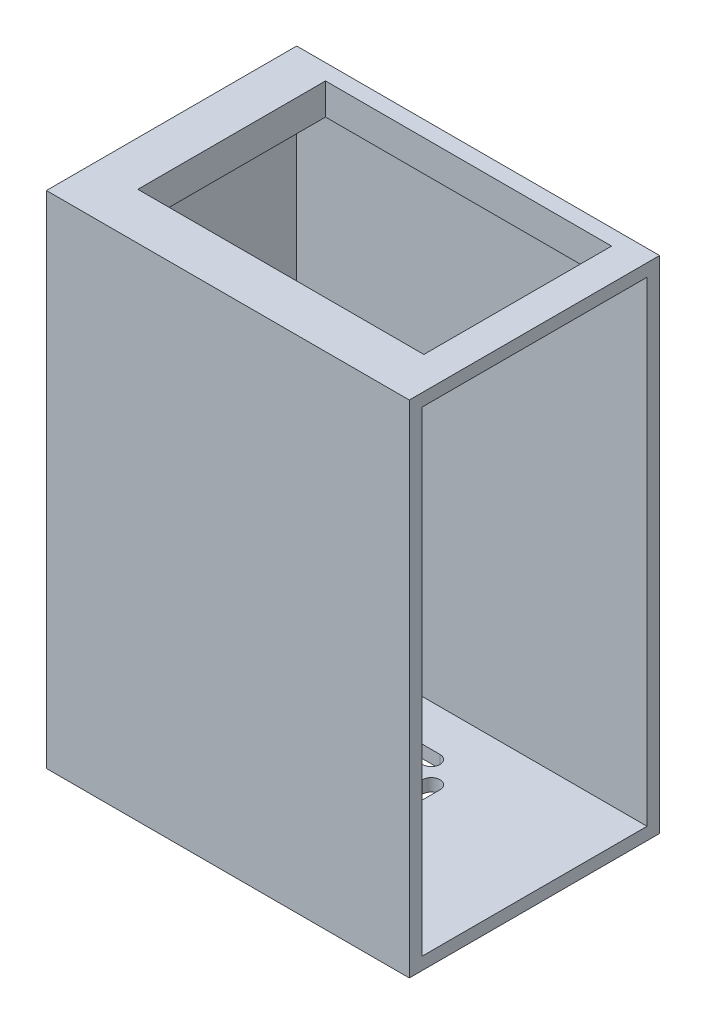
SolidWorks part; units mm, degrees
ref_plane "Front Plane" through (0, 0, 0) normal (0, 0, 1) x (1, 0, 0)
ref_plane "Top Plane" through (0, 0, 0) normal (0, 1, 0) x (1, 0, 0)
ref_plane "Right Plane" through (0, 0, 0) normal (1, 0, 0) x (0, 0, -1)
sketch "Sketch1" plane through (0, 0, 0) normal (0, 0, 1) x (1, 0, 0)
  line L1 (-38.1, -50.8) -> (38.1, -50.8)
  line L2 (-38.1, -50.8) -> (-38.1, 50.8)
  line L3 (-38.1, 50.8) -> (38.1, 50.8)
  line L4 (38.1, -50.8) -> (38.1, 50.8)
  line L5 (-38.1, -50.8) -> (38.1, 50.8) construction
  line L6 (-38.1, 50.8) -> (38.1, -50.8) construction
  point P0 (0, 0)
  dimension "D1" = 76.2
  dimension "D2" = 101.6
extrude "body" add sketch "Sketch1" along normal blind 50.8
sketch "Sketch2" plane through (0, 50.8, 0) normal (0, 1, 0) x (1, 0, 0)
  line L0 (38.1, 0) -> (-38.1, 0) construction
  line L1 (29.0322, -41.3147) -> (-29.0322, -41.3147)
  line L2 (29.0322, -41.3147) -> (29.0322, -3.2147)
  line L3 (29.0322, -3.2147) -> (-29.0322, -3.2147)
  line L4 (-29.0322, -41.3147) -> (-29.0322, -3.2147)
  line L5 (29.0322, -41.3147) -> (-29.0322, -3.2147) construction
  line L6 (29.0322, -3.2147) -> (-29.0322, -41.3147) construction
  point P0 (0, -22.2647)
  point P8 (0, 0)
  dimension "D1" = 38.1
  dimension "D2" = 58.0644
  dimension "D3" = 0
extrude "camera hole" cut sketch "Sketch2" against normal blind 6.35
shell "hollow" thickness 2.54 removed face at (0, 44.45, 22.2647)
sketch "centre of button holes" plane through (0, -50.8, 0) normal (0, -1, 0) x (-1, 0, 0)
  point P0 (0, -19.05)
  dimension "D1" = 19.05
sketch "Sketch4" plane through (0, -50.8, 0) normal (0, -1, 0) x (1, 0, 0)
  line L0 (6.35, 20.955) -> (6.35, 17.145) construction
  line L1 (8.128, 20.955) -> (8.128, 17.145)
  line L2 (4.572, 20.955) -> (4.572, 17.145)
  arc A0 (8.128, 20.955) -> (4.572, 20.955) centre (6.35, 20.955) ccw
  arc A1 (4.572, 17.145) -> (8.128, 17.145) centre (6.35, 17.145) ccw
  point P2 (6.35, 19.05)
  dimension "D3" = 1.778
  dimension "D1" = 6.35
  dimension "D2" = 3.81
extrude "single button leg hole" cut sketch "Sketch4" against normal up to next
ref_axis "axis of button" through (0, -50.8, 19.05) along (0, -1, 0)
pattern_circular "all button holes" count 4 over 360 about axis through (0, -50.8, 19.05) along (0, -1, 0) of "single button leg hole"
sketch "Sketch5" plane through (38.1, 0, 0) normal (1, 0, 0) x (0, 0, -1)
  line L1 (0, -50.8) -> (-50.8, -50.8)
  line L2 (0, -50.8) -> (0, 50.8)
  line L3 (0, 50.8) -> (-50.8, 50.8)
  line L4 (-50.8, -50.8) -> (-50.8, 50.8)
extrude "let folks see in" cut sketch "Sketch5" against normal blind 2.54
